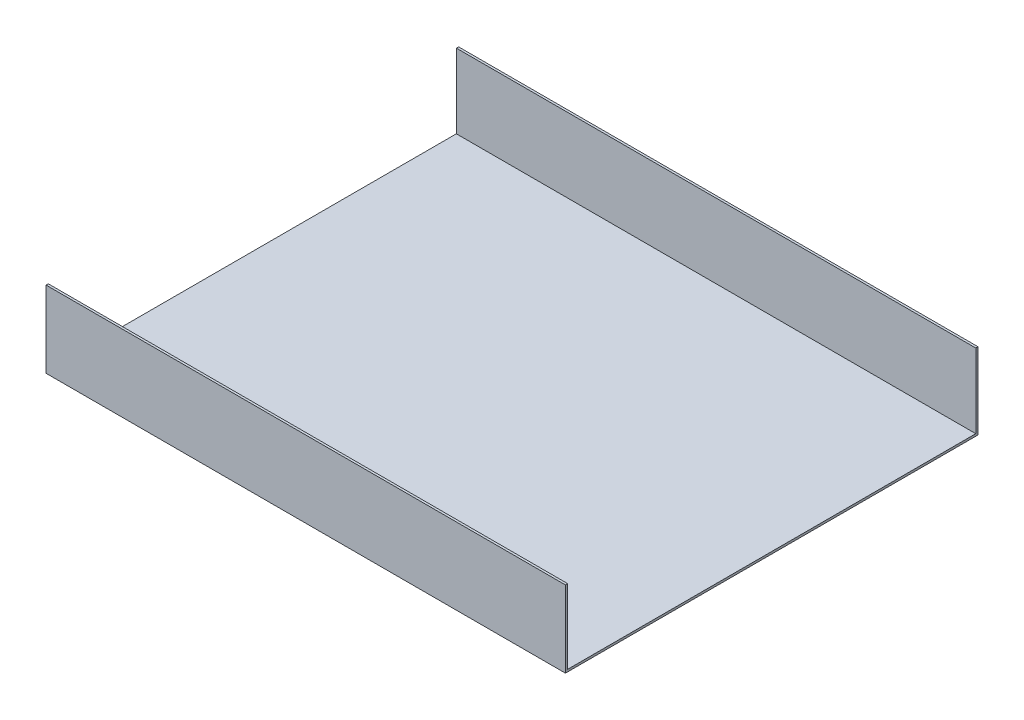
SolidWorks part; units mm, degrees
material "AISI 304"
ref_plane "Alzado" through (0, 0, 0) normal (0, 0, 1) x (1, 0, 0)
ref_plane "Planta" through (0, 0, 0) normal (0, 1, 0) x (1, 0, 0)
ref_plane "Vista lateral" through (0, 0, 0) normal (1, 0, 0) x (0, 0, -1)
sketch "Croquis1" plane through (0, 0, 0) normal (1, 0, 0) x (0, 0, -1)
  line L0 (0, 20) -> (0, 0)
  line L1 (0, 0) -> (110, 0)
  line L2 (110, 0) -> (110, 20)
  line L3 (0, 20) -> (110, 20)
  dimension "D1" = 110
  dimension "D2" = 20
extrude "Saliente-Extruir1" add sketch "Croquis1" along normal blind 140
shell "Vaciado1" thickness 0.6 removed face at (0, 10, -55) removed face at (140, 10, -55) removed face at (70, 20, -55) outward yes
